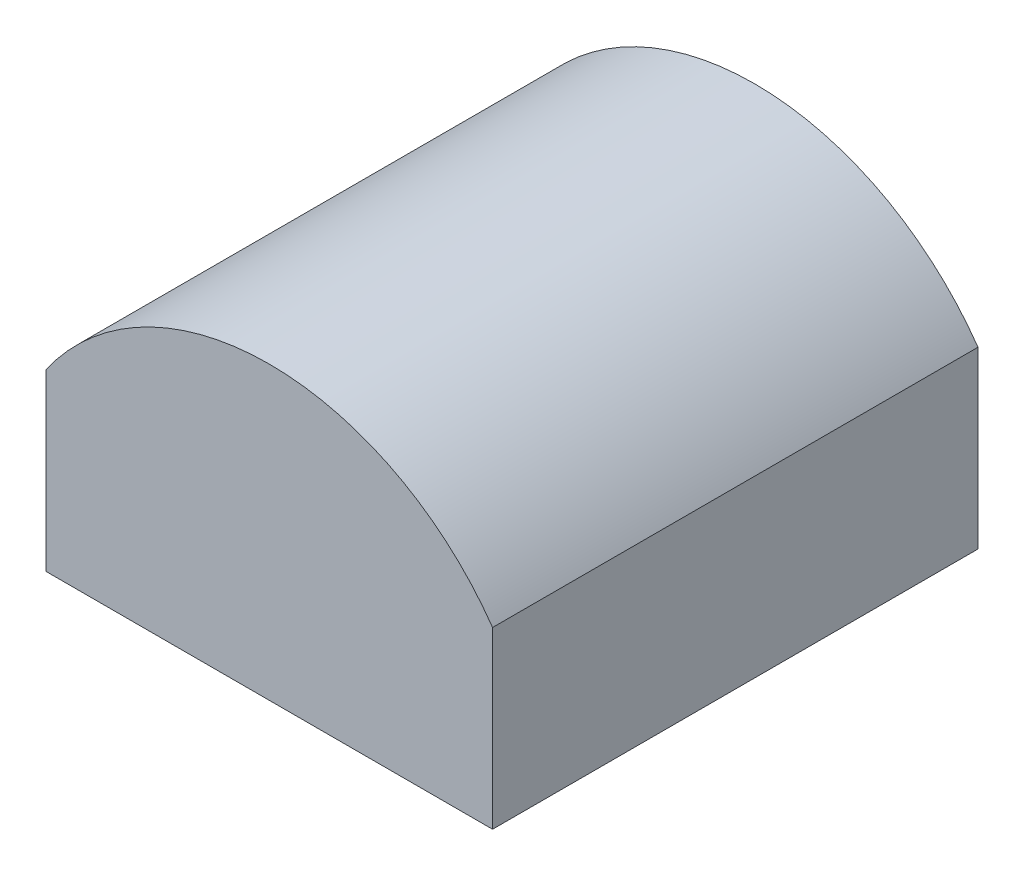
SolidWorks part; units mm, degrees
ref_plane "前基準面" through (0, 0, 0) normal (0, 0, 1) x (1, 0, 0)
ref_plane "上基準面" through (0, 0, 0) normal (0, 1, 0) x (1, 0, 0)
ref_plane "右基準面" through (0, 0, 0) normal (1, 0, 0) x (0, 0, -1)
sketch "草圖1" plane through (0, 0, 0) normal (0, 0, 1) x (1, 0, 0)
  line L0 (-11.1819, 3.1383) -> (-11.1819, -5.8617)
  line L2 (-8.1819, 3.1383) -> (-8.1819, -2.8617)
  line L3 (-8.1819, -2.8617) -> (8.8181, -2.8617)
  line L4 (8.8181, 3.1383) -> (8.8181, -2.8617)
  line L5 (-11.1819, -5.8617) -> (11.8181, -5.8617)
  line L6 (11.8181, -5.8617) -> (11.8181, 3.1383)
  arc A0 (-8.1819, 3.1383) -> (8.8181, 3.1383) centre (0.3181, -7.4033) cw
  arc A1 (-11.1819, 3.1383) -> (11.8181, 3.1383) centre (0.3181, -4.8825) cw
  point P6 (0.3181, 6.1383)
  point P11 (-8.1819, 0.1383)
  point P12 (0.3181, 9.1383)
  dimension "D6" = 3
  dimension "D1" = 17
  dimension "D2" = 6
  dimension "D3" = 3
  dimension "D4" = 3
  dimension "D5" = 3
extrude "填料-伸長1" add sketch "草圖1" along normal blind 5 contours L2 L3 L4 A0
extrude "填料-伸長2" add sketch "草圖1<4>" against normal blind 20 and the other way blind 5
sketch "草圖1<4>" plane through (0, 0, 0) normal (0, 0, 1) x (1, 0, 0) same geometry as "草圖1"
